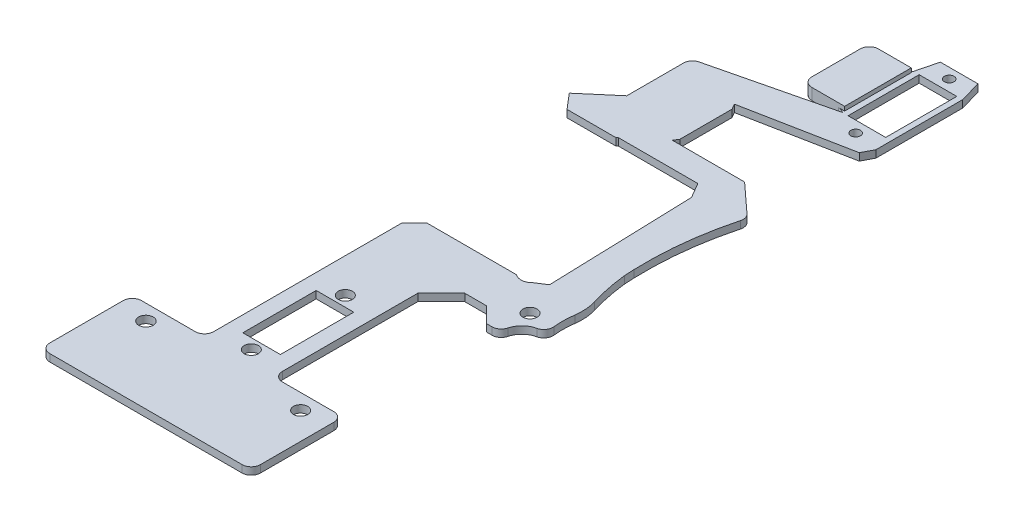
SolidWorks part; units mm, degrees
note: The reader was unsure of these and kept them because the rebuilt part matched: shared geometry of "焊点<3>".
material "A-玻璃纤维"
ref_plane "前视基准面" through (0, 0, 0) normal (0, 0, 1) x (1, 0, 0)
ref_plane "上视基准面" through (0, 0, 0) normal (0, 1, 0) x (1, 0, 0)
ref_plane "右视基准面" through (0, 0, 0) normal (1, 0, 0) x (0, 0, -1)
sketch "草图1" plane through (0, 0, 0) normal (0, 1, 0) x (1, 0, 0)
  line L0 (0, 0) -> (0, 93.7155) construction
  line L1 (-1000, 0) -> (49000, 0) construction
  line L2 (18.4, 78.6494) -> (31.6, 78.6494) construction
  line L3 (31.6, 78.6494) -> (31.6, -20.2231) construction
  line L4 (31.6, -20.2231) -> (7.5, -20.2231) construction
  line L5 (7.5, -20.2231) -> (7.5, -53.5008) construction
  line L6 (7.5, -53.5008) -> (-7.5, -53.5008) construction
  line L7 (-7.5, -53.5008) -> (-7.5, -7.7231) construction
  line L8 (-7.5, -7.7231) -> (18.4, -7.7231) construction
  line L9 (18.4, -7.7231) -> (18.4, 78.6494) construction
  line L14 (20.9, 73.9628) -> (29.1, 73.9628)
  line L19 (29.1, 73.9628) -> (29.1, 58.4628)
  line L20 (29.1, 58.4628) -> (20.9, 58.4628)
  line L21 (20.9, 73.9628) -> (18.4, 73.9628) construction
  line L22 (29.1, 73.9628) -> (31.6, 73.9628) construction
  line L23 (-4.1, -32.5354) -> (4.1, -32.5354)
  line L24 (4.1, -32.5354) -> (4.1, -48.5372)
  line L25 (4.1, -48.5372) -> (-4.1, -48.5372)
  line L26 (-4.1, -48.5372) -> (-4.1, -32.5354)
  line L31 (20.9, 58.4628) -> (20.9, 73.9628)
  line L32 (17.6249, -7.7231) -> (-4.6916, -7.7231)
  line L33 (0.2153, -9.2231) -> (-5.2847, -9.2231) construction
  line L34 (20.8422, 78.6494) -> (29.0422, 78.6494)
  line L35 (29.0422, 78.6494) -> (30.35, 73.9628)
  line L36 (20.8422, 78.6494) -> (19.65, 73.9628)
  line L37 (19.65, 73.9628) -> (19.65, 58.4628)
  line L38 (30.35, 73.9628) -> (30.35, 55.0889)
  line L39 (30.35, 55.0889) -> (29.1, 52.6978)
  line L43 (-4.6916, -7.7231) -> (-7.5, -10.5315)
  line L44 (25, 58.4628) -> (25, 73.9628) construction
  line L46 (29.8202, -19.2171) -> (26.7744, -20.2231)
  line L49 (7.5, -21.9858) -> (7.5, -53.5008)
  line L50 (-7.5, -10.5315) -> (-7.5, -53.5008)
  line L54 (26.7744, -20.2231) -> (20.682, -20.2231)
  line L55 (20.682, -20.2231) -> (17.3152, -16.8563)
  line L56 (17.3152, -16.8563) -> (12.6295, -16.8563)
  line L57 (12.6295, -16.8563) -> (7.5, -21.9858)
  line L58 (19.65, 58.4628) -> (-7, 52.0097)
  line L59 (7.5, -53.5008) -> (22.7112, -53.5008)
  line L60 (22.7112, -53.5008) -> (22.7112, -73.5008)
  line L61 (22.7112, -73.5008) -> (-23.232, -73.5008)
  line L62 (-23.232, -73.5008) -> (-23.232, -53.5008)
  line L63 (-23.232, -53.5008) -> (-7.5, -53.5008)
  line L64 (-7, 52.0097) -> (-7, 37.4909)
  line L65 (-7, 37.4909) -> (0, 29.2769)
  line L69 (29.1, 52.6978) -> (6.3315, 48.2555)
  line L71 (7, 47.064) -> (7, 35.6651)
  line L72 (6.35, 34.6651) -> (18.4, 34.6651)
  line L73 (18.4, 34.6651) -> (22.1247, 34.6651)
  line L74 (22.1247, 34.6651) -> (29.8202, 27.6136)
  line L75 (29.8202, 27.6136) -> (29.8202, -19.2171)
  line L76 (17.3145, 29.2769) -> (19.254, 25.9571)
  line L77 (19.254, 25.9571) -> (20.2694, -6.0079)
  line L78 (20.2694, -6.0079) -> (17.6249, -7.7231)
  line L79 (17.3145, 29.2769) -> (0, 29.2769)
  line L80 (8.1403, 28.2769) -> (-6.1097, 28.2769) construction
  line L81 (7, 35.6651) -> (6.35, 34.6651)
  line L82 (6.3315, 48.2555) -> (7, 47.064)
  circle A5 centre (0, -30.2872) radius 1.55
  circle A6 centre (0, -50.7872) radius 1.55
  circle A8 centre (25, 76.4128) radius 1.05
  circle A9 centre (25, 56.0128) radius 1.05
  circle A10 centre (23.5, -13.5) radius 1.55
  circle A11 centre (-16.866, -56.8953) radius 1.5814
  circle A12 centre (16.866, -56.8953) radius 1.55
  arc A13 (34.2984, 60.9175) -> (37.7098, 63.0438) centre (0, 119.7445) ccw construction
  arc A14 (29.8202, 27.6136) -> (23.8014, 22.6423) centre (52.8883, -6.4445) ccw construction
  arc A15 (29.8202, 27.6136) -> (29.8202, -11.188) centre (91.9966, 8.2128) ccw construction
  dimension "D5" = 3.1
  dimension "D11" = 45.9432
  dimension "D12" = 20
  dimension "D1" = 8.2
  dimension "D2" = 16.0019
  dimension "D3" = 1.5
  dimension "D4" = 12.5
  dimension "D6" = 23.5
  dimension "D7" = 13.5
  dimension "D8" = 1.25
  dimension "D9" = 135
  dimension "D10" = 1
  dimension "D13" = 135
  dimension "D14" = 135
  dimension "D15" = 1
  dimension "D16" = 139.562
  dimension "D17" = 0.5
  dimension "D18" = 0.5
  dimension "D19" = 1
extrude "凸台-拉伸1" add sketch "草图1" along normal blind 1.6
sketch "限位裁切" plane through (0, 0, 0) normal (0, 1, 0) x (1, 0, 0)
  line L1 (29.8212, 31.3086) -> (29.8201, -18.1642)
  line L2 (29.8202, -19.2171) -> (29.8202, 27.6136) construction
  line L3 (29.8211, 28.9135) -> (29.8202, -16.0617) construction
  line L7 (26.9026, 5.9628) -> (27.0025, 3.9628) construction
  line L8 (0, 0) -> (103.2503, 0) construction
  line L9 (0, 0) -> (0, -91.5316) construction
  line L10 (26.6107, 6.0628) -> (26.7207, 3.8628)
  line L11 (26.9525, 4.9628) -> (29.8206, 4.9628) construction
  circle A0 centre (28, -19.7872) radius 3.15 construction
  arc A2 (28.7446, -8.9732) -> (29.8201, -18.1642) centre (46.8897, -11.5083) ccw
  circle A4 centre (28, -19.7872) radius 3.15 construction
  circle A6 centre (28, -19.7872) radius 4.25
  circle A8 centre (16.2653, -5.7231) radius 2.5
  circle A9 centre (28, 36.2128) radius 3.15 construction
  circle A10 centre (28, 36.2128) radius 3.15 construction
  circle A11 centre (28, 36.2128) radius 4.25
  arc A12 (26.9026, 5.9628) -> (29.4289, 26.3118) centre (91.9966, 8.2128) cw construction
  arc A13 (26.6107, 6.0628) -> (29.3897, 28.4467) centre (98.2142, 8.5378) cw
  arc A14 (26.7207, 3.8628) -> (28.3863, -4.2895) centre (72.7235, 9.0154) ccw
  arc A15 (29.4289, 26.3118) -> (29.8211, 28.9135) centre (19.8227, 29.0906) ccw construction
  arc A16 (27.0025, 3.9628) -> (28.5167, -3.4484) centre (68.8233, 8.647) ccw construction
  arc A17 (28.5167, -3.4484) -> (28.8424, -7.7063) centre (18.9386, -6.3226) cw construction
  arc A18 (28.8424, -7.7063) -> (35.5479, -23.4857) centre (45.3379, -10.0109) ccw construction
  arc A19 (28.8424, -7.7063) -> (29.8202, -16.0617) centre (45.3379, -10.0109) ccw construction
  arc A20 (28.3863, -4.2895) -> (28.7446, -8.9732) centre (17.8504, -7.4511) cw
  arc A21 (29.3897, 28.4467) -> (29.8212, 31.3086) centre (18.8229, 31.5033) ccw
  dimension "D3" = 8.5
  dimension "D4" = 5
extrude "切除-拉伸5" cut sketch "限位裁切" along normal through all contours A2 A6 L1 | A21 A13 L10 A14 A20 A2 A6 L1 | A11 | A8 | L1 A6 A2
sketch "焊点" plane through (0, 0, 0) normal (0, 1, 0) x (1, 0, 0)
  line L0 (-5.2847, -7.7231) -> (0.2153, -7.7231) construction
  line L1 (14.7653, -7.7231) -> (-4.6916, -7.7231) construction
  line L2 (0.2153, -7.7231) -> (0.2153, -13.7231)
  line L3 (0.2153, -13.7231) -> (-5.2847, -13.7231)
  line L4 (-5.2847, -13.7231) -> (-5.2847, -7.7231) construction
  line L5 (-0.2153, -7.7231) -> (5.2847, -7.7231)
  line L6 (5.2847, -7.7231) -> (5.2847, -13.7231)
  line L7 (5.2847, -13.7231) -> (-0.2153, -13.7231)
  line L8 (-0.2153, -13.7231) -> (-0.2153, -7.7231)
  line L9 (0, 0) -> (0, -6.2862) construction
  line L10 (0.2153, -13.7231) -> (0.2153, -9.2231) construction
  line L11 (-5.2847, -9.2231) -> (-5.2847, -13.7231) construction
  line L12 (-5.2847, -13.7231) -> (-4.2847, -13.7231) construction
  line L13 (0.2153, -7.7231) -> (-4.6916, -7.7231)
  line L14 (-4.6916, -7.7231) -> (-5.2847, -8.3162)
  line L15 (-4.6916, -7.7231) -> (-7.5, -10.5315) construction
  line L16 (-5.2847, -8.3162) -> (-5.2847, -13.7231)
  line L17 (10.5, 73.4878) -> (19.65, 73.4878)
  line L18 (5.2847, -13.7231) -> (5.2847, -15.2731)
  line L19 (19.65, 73.4878) -> (19.65, 58.9628)
  line L20 (19.65, 58.9628) -> (10.5, 58.9628)
  line L21 (10.5, 58.9628) -> (10.5, 73.4878)
  line L22 (20.9, 73.9628) -> (20.9, 58.4628) construction
  line L23 (20.9, 58.4628) -> (29.1, 58.4628) construction
  line L24 (-5.2847, -13.7231) -> (-5.2847, -19.2231)
  line L25 (-5.2847, -19.2231) -> (0.2153, -19.2231)
  line L26 (0.2153, -19.2231) -> (0.2153, -13.7231)
  line L27 (-0.2153, -13.7231) -> (-0.2153, -19.2231)
  line L28 (-0.2153, -19.2231) -> (5.2847, -19.2231) construction
  line L29 (5.2847, -19.2231) -> (5.2847, -13.7231) construction
  line L30 (5.2847, -15.2731) -> (1.3347, -19.2231)
  line L31 (1.3347, -19.2231) -> (-0.2153, -19.2231)
  dimension "D1" = 9.15
  dimension "D2" = 14.525
  dimension "D3" = 1.25
  dimension "D4" = 0.5
  dimension "D5" = 5.5
  dimension "D6" = 135
  dimension "D7" = 1.55
extrude "电调焊点" add sketch "焊点" against normal blind 0.5 contours L14 L16 L3 L2 L13 | L8 L7 L6 L5 | L31 L30 L18 L7 L27 | L25 L26 L3 L24
extrude "JST-GH-4Pin x 2" add sketch "焊点<3>" along normal blind 2.5 from surface at 0 contours L21 L20 L19 L17 starting at face at (11.591, 0, -5.175)
sketch "焊点<3>" plane through (0, 0, 0) normal (0, 1, 0) x (1, 0, 0) same geometry as "焊点"
fillet "圆角3" radius 2 14 edges at (19.65, 0.8, -58.9628) (10.5, 1.25, -58.9628) (10.5, 1.25, -73.4878) (19.65, 0.8, -73.4878) (-7, 0.8, -52.0097) (23.7724, 0.8, 20.2231) (-23.232, 0.8, 73.5008) (22.7112, 0.8, 73.5008) (22.7112, 0.8, 53.5008) (7.5, 0.8, 53.5008) (-7.5, 0.8, 53.5008) (-23.232, 0.8, 53.5008) (29.2901, 0.8, -28.0993) (29.0469, 0.8, 15.6682)
sketch "草图3" plane through (0, 1.6, 0) normal (0, 1, 0) x (1, 0, 0)
  line L8 (-13.7664, 32.3261) -> (-10.9435, 29.0136)
  line L12 (-10.9435, 29.0136) -> (-0.3089, 29.0136)
  line L16 (0, 29.2769) -> (-6.4695, 23.7636) construction
  line L17 (-7, 37.4909) -> (0, 29.2769) construction
  line L18 (-6.4695, 23.7636) -> (-13.7664, 32.3261) construction
  line L22 (-7, 37.4909) -> (0, 29.2769)
  line L24 (0, 29.2769) -> (-0.3089, 29.0136)
  line L26 (-13.7664, 32.3261) -> (-7, 38.0925)
  line L27 (-7, 50.4362) -> (-7, 37.4909) construction
  line L28 (-7, 38.0925) -> (-7, 37.4909)
  dimension "D1" = 11.25
  dimension "D2" = 8.5
  dimension "D4" = 5.25
extrude "串口插头" add sketch "草图3" along normal up to surface (1.6 mm away) from surface at -1.6 up to face at (12.9584, 1.6, -5.8762) starting at face at (11.0903, 0, -5.2057)
